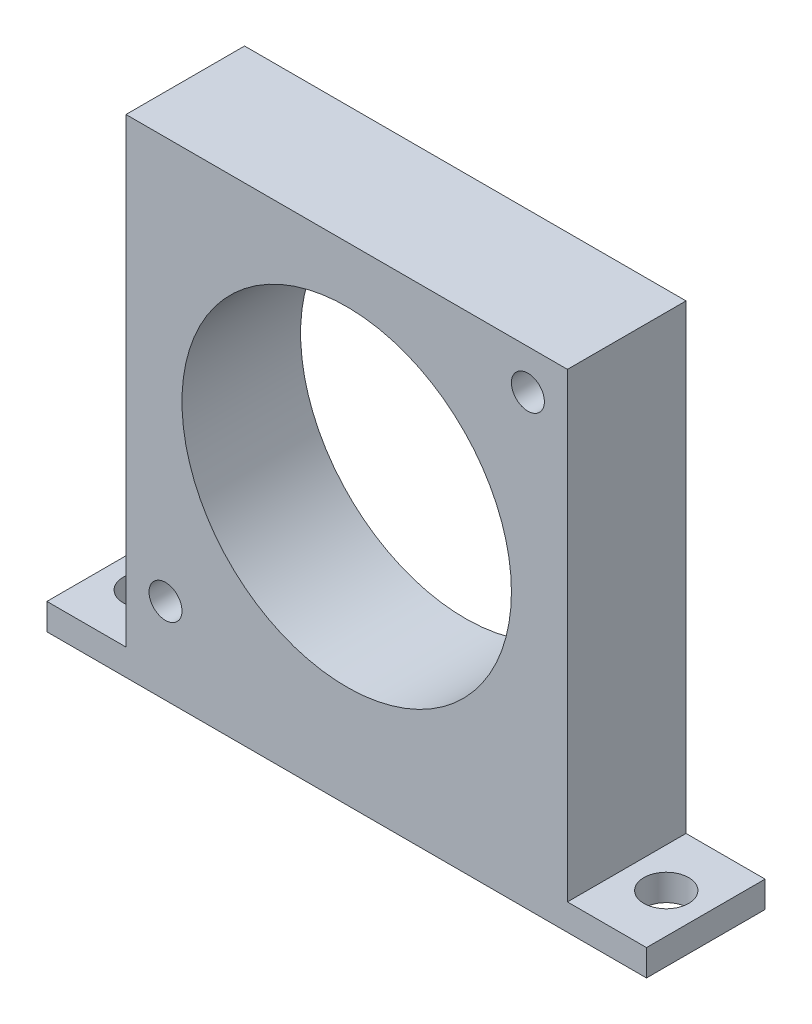
SolidWorks part; units mm, degrees
ref_plane "Front Plane" through (0, 0, 0) normal (0, 0, 1) x (1, 0, 0)
ref_plane "Top Plane" through (0, 0, 0) normal (0, 1, 0) x (1, 0, 0)
ref_plane "Right Plane" through (0, 0, 0) normal (1, 0, 0) x (0, 0, -1)
sketch "Sketch1" plane through (0, 0, 0) normal (0, 0, 1) x (1, 0, 0)
  line L0 (22.75, 0) -> (22.75, 37) construction
  line L1 (0, 0) -> (45.5, 0)
  line L2 (0, 0) -> (0, 2)
  line L3 (0, 2) -> (6, 2)
  line L4 (45.5, 0) -> (45.5, 2)
  line L5 (39.5, 2) -> (39.5, 37)
  line L6 (39.5, 37) -> (6, 37)
  line L7 (6, 2) -> (6, 37)
  line L8 (39.5, 2) -> (45.5, 2)
  dimension "D1" = 35
  dimension "D2" = 33.5
  dimension "D3" = 2
  dimension "D4" = 6
extrude "Boss-Extrude1" add sketch "Sketch1" along normal blind 9 contours L7 L6 L5 L8 L4 L1 L2 L3
hole_wizard "M3x0.5 Tapped Hole1" positions "3DSketch1" profile "Sketch2" tap size "M3x0.5" standard "ANSI Metric" end condition through all
sketch3d "3DSketch1"
  line L0 (39.5, 2, 9) -> (39.5, 37, 9) construction
  line L1 (39.5, 37, 9) -> (6, 37, 9) construction
  line L4 (6, 2, 9) -> (6, 37, 9) construction
  point P0 (36.5, 34, 9)
  point P2 (9, 6.5, 9)
  dimension "D1" = 3
  dimension "D2" = 3
  dimension "D3" = 30.5
  dimension "D4" = 3
sketch "Sketch2" plane through (36.5, 34, 9) normal (1, 0, 0) x (0, -1, 0)
  line L0 (0, 0) -> (0, 9)
  line L1 (0, 9) -> (1.25, 9)
  line L2 (1.25, 9) -> (1.25, 0)
  line L5 (1.25, 0) -> (0, 0)
  line L11 (0, -6.35) -> (0, 107.95) construction
  dimension "Thread Major Dia." = 2.5
  dimension "Thru Tap Drill Depth" = 9
hole_wizard "M3 Clearance Hole2" positions "3DSketch2" profile "Sketch5" hole size "M3" standard "ANSI Metric" end condition through all
sketch3d "3DSketch2"
  line L0 (39.5, 2, 9) -> (45.5, 2, 9) construction
  line L1 (0, 2, 9) -> (6, 2, 9) construction
  line L2 (6, 2, 0) -> (6, 2, 9) construction
  point P0 (42.5, 2, 4.5)
  point P2 (3, 2, 4.5)
  point P8 (42.5, 2, 9)
  point P11 (3, 2, 9)
  point P17 (6, 2, 4.5)
sketch "Sketch5" plane through (42.5, 2, 4.5) normal (1, 0, 0) x (0, 0, 1)
  line L0 (0, 0) -> (0, 2)
  line L1 (0, 2) -> (1.7, 2)
  line L2 (1.7, 2) -> (1.7, 0)
  line L5 (1.7, 0) -> (0, 0)
  line L11 (0, -6.35) -> (0, 107.95) construction
  dimension "Thru Hole Dia." = 3.4
  dimension "Thru Hole Depth" = 2
hole_wizard "Ø25.0mm Dowel Hole1" positions "Sketch8" profile "Sketch7" hole size "Ø25.0" standard "ANSI Metric" end condition through all
sketch "Sketch8" plane through (0, 0, 9) normal (0, 0, 1) x (1, 0, 0)
  line L0 (9, 6.5) -> (36.5, 34) construction
  point P0 (22.75, 20.25)
  point P10 (22.75, 20.25)
sketch "Sketch7" plane through (22.75, 20.25, 9) normal (1, 0, 0) x (0, -1, 0)
  line L0 (0, 0) -> (0, 9)
  line L1 (0, 9) -> (12.5, 9)
  line L2 (12.5, 9) -> (12.5, 0)
  line L5 (12.5, 0) -> (0, 0)
  line L11 (0, -6.35) -> (0, 107.95) construction
  dimension "Thru Hole Dia." = 25
  dimension "Thru Hole Depth" = 9
